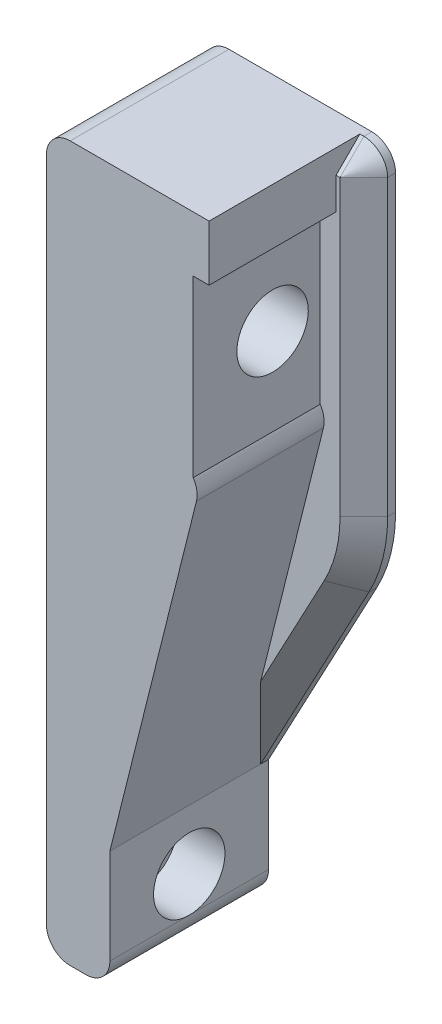
SolidWorks part; units mm, degrees
ref_plane "Front Plane" through (0, 0, 0) normal (0, 0, 1) x (1, 0, 0)
ref_plane "Top Plane" through (0, 0, 0) normal (0, 1, 0) x (1, 0, 0)
ref_plane "Right Plane" through (0, 0, 0) normal (1, 0, 0) x (0, 0, -1)
sketch "Sketch1" plane through (0, 0, 0) normal (0, 0, 1) x (1, 0, 0)
  line L1 (0, 0) -> (24, 0)
  line L2 (0, 0) -> (0, 90)
  line L3 (0, 90) -> (24, 90)
  line L4 (24, 0) -> (24, 90)
  dimension "D1" = 90
  dimension "D2" = 24
extrude "Boss-Extrude1" add sketch "Sketch1" against normal blind 20
sketch "Sketch4" plane through (0, 0, 0) normal (0, 0, 1) x (1, 0, 0)
  line L2 (0, 0) -> (24, 0) construction
  line L3 (20.5, 83) -> (18.5, 83)
  line L4 (18.5, 83) -> (18.5, 61)
  line L8 (24, 90) -> (24, 0)
  line L9 (24, 0) -> (24, 90) construction
  line L11 (18.5, 61) -> (19.5, 61)
  line L13 (20.5, 83) -> (20.5, 90)
  line L14 (24, 90) -> (0, 90) construction
  line L15 (20.5, 90) -> (24, 90)
  line L16 (8, 0) -> (24, 0)
  line L17 (8, 0) -> (8, 15)
  line L18 (19.5, 61) -> (8, 15)
  dimension "D1" = 5.5
  dimension "D2" = 2
  dimension "D3" = 8
  dimension "D4" = 22
  dimension "D5" = 1
  dimension "D6" = 7
  dimension "D7" = 15
extrude "Cut-Extrude1" cut sketch "Sketch4" against normal blind 16
ref_plane "Plane1" through (0, 0, -20) normal (0, 0, -1) x (-1, 0, 0)
ref_plane "Plane2" through (0, 0, 0) normal (-1, 0, 0) x (0, 0, 1)
ref_plane "Plane3" through (18.5, 0, 0) normal (1, 0, 0) x (0, 0, -1)
sketch "Sketch8" plane through (18.5, 0, 0) normal (1, 0, 0) x (0, 0, -1)
  line L0 (0, 83) -> (0, 61) construction
  circle A0 centre (10, 71.6432) radius 2.5
  circle A1 centre (10, 21.6432) radius 2.5
  dimension "D1" = 10
  dimension "D2" = 50
sketch "Sketch9" plane through (0, 0, -20) normal (0, 0, -1) x (-1, 0, 0)
  line L2 (-24, 0) -> (-24, 45)
  line L4 (-8, 15) -> (-8, 0)
  line L5 (-8, 0) -> (-24, 0)
  line L9 (-24, 0) -> (-24, 90) construction
  line L10 (-24, 45) -> (-8, 15)
extrude "Cut-Extrude8" cut sketch "Sketch9" against normal blind 10
sketch "Sketch11" plane through (18.5, 0, 0) normal (1, 0, 0) x (0, 0, -1)
  line L0 (0, 72) -> (16, 72)
  line L1 (0, 83) -> (0, 61) construction
  line L2 (16, 83) -> (16, 61) construction
  line L3 (0, 7.5) -> (16, 7.5)
  line L4 (0, 15) -> (0, 0) construction
  circle A0 centre (8, 72) radius 2.5
  circle A1 centre (8, 7.5) radius 2.5
  circle A2 centre (8, 72) radius 4.5
  circle A3 centre (8, 7.5) radius 4.5
  dimension "D1" = 5
fillet "Fillet1" radius 20 1 edges at (24, 45, -18)
sketch "Sketch12" plane through (18.5, 0, 0) normal (1, 0, 0) x (0, 0, -1)
  line L0 (10, 90) -> (10, 0)
  line L1 (20, 90) -> (0, 90) construction
  line L2 (20, 0) -> (0, 0) construction
  line L3 (0, 72) -> (16, 72)
  line L4 (0, 83) -> (0, 61) construction
  line L5 (16, 83) -> (16, 61) construction
  line L6 (0, 7.5) -> (20, 7.5)
  line L7 (0, 15) -> (0, 0) construction
  line L8 (20, 0) -> (20, 15) construction
  circle A0 centre (10, 72) radius 2.5
  circle A1 centre (10, 7.5) radius 2.5
  dimension "D1" = 10
extrude "Cut-Extrude9" cut sketch "Sketch12" against normal blind 18.5 contours A1 | A0
sketch "Sketch13" plane through (18.5, 0, 0) normal (1, 0, 0) x (0, 0, -1)
  circle A0 centre (10, 72) radius 4.5
  circle A1 centre (10, 7.5) radius 4.5
extrude "Cut-Extrude10" cut sketch "Sketch13" against normal blind 16.5
fillet "Fillet2" radius 3 5 edges at (0, 90, -10) (24, 90, -18) (19.5, 61, -8) (8, 0, -10) (0, 0, -10)
chamfer "Chamfer1" distance 3 angle 45 5 edges at (20.75, 90, -16) (23.1213, 89.1213, -16) (24, 68.5, -16) (23.4029, 45.1493, -16) (14.8235, 27.7941, -16)
